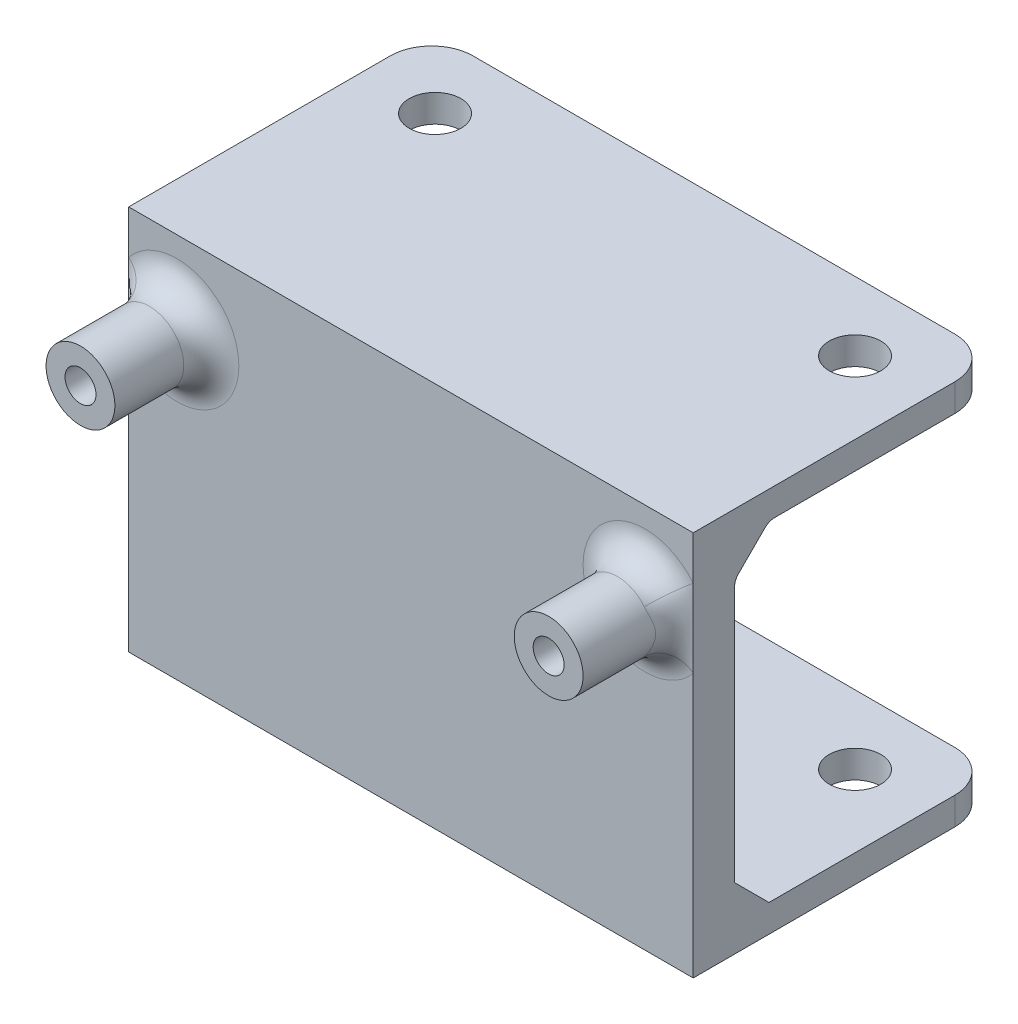
SolidWorks part; units mm, degrees
ref_plane "前视基准面" through (0, 0, 0) normal (0, 0, 1) x (1, 0, 0)
ref_plane "上视基准面" through (0, 0, 0) normal (0, 1, 0) x (1, 0, 0)
ref_plane "右视基准面" through (0, 0, 0) normal (1, 0, 0) x (0, 0, -1)
other "Configuration Table"
sketch "草图1" plane through (0, 0, 0) normal (0, 1, 0) x (1, 0, 0)
  line L0 (-15.25, 6) -> (15.25, 6) construction
  line L1 (-20.5, 11) -> (20.5, 11)
  line L2 (-20.5, 11) -> (-20.5, -11)
  line L3 (-20.5, -11) -> (20.5, -11)
  line L4 (20.5, 11) -> (20.5, -11)
  line L5 (-20.5, 0) -> (20.5, 0) construction
  circle A0 centre (-15.25, 6) radius 1.875
  circle A1 centre (15.25, 6) radius 1.875
  point P10 (0, 0)
  point P11 (0, 6)
  dimension "D3" = 3.75
  dimension "D4" = 3.75
  dimension "D1" = 41
  dimension "D2" = 22
  dimension "D5" = 30.5
  dimension "D6" = 5
extrude "凸台-拉伸1" add sketch "草图1" against normal blind 2
sketch "草图2" plane through (0, 0, 11) normal (0, 0, 1) x (1, 0, 0)
  line L0 (-17, -6) -> (17, -6) construction
  line L1 (-20.5, -2) -> (20.5, -2)
  line L2 (-20.5, -2) -> (-20.5, -28)
  line L3 (-20.5, -28) -> (20.5, -28)
  line L4 (20.5, -2) -> (20.5, -28)
  circle A0 centre (-17, -6) radius 1.125
  circle A1 centre (17, -6) radius 1.125
  point P4 (0, -6)
  dimension "D1" = 2.25
  dimension "D2" = 2.25
  dimension "D3" = 34
  dimension "D4" = 4
  dimension "D5" = 26
extrude "凸台-拉伸2" add sketch "草图2" against normal blind 3
ref_plane "基准面2" through (20.5, -2, 8) normal (-1, 0, 0) x (0, 0, 1)
sketch "草图5" plane through (20.5, -2, 8) normal (-1, 0, 0) x (0, 0, 1)
  line L0 (-2.5, 0) -> (0, -2.5)
  line L1 (-19, 0) -> (0, 0) construction
  line L2 (0, 0) -> (0, -26) construction
  line L3 (-2.5, 0) -> (0, 0)
  line L4 (0, 0) -> (0, -2.5)
  dimension "D1" = 2.5
  dimension "D2" = 2.5
extrude "凸台-拉伸3" add sketch "草图5" along normal up to surface (41 mm away) up to face at (-20.5, -10, 2.6667)
fillet "圆角1" radius 3 2 edges at (20.5, -1, -11) (-20.5, -1, -11)
fillet "圆角2" radius 1 2 edges at (0, -4.5, 8) (0, -2, 5.5)
sketch "草图6" plane through (0, 0, 11) normal (0, 0, 1) x (1, 0, 0)
  circle A0 centre (-17, -6) radius 2.5
  circle A1 centre (17, -6) radius 2.5
  circle A2 centre (-17, -6) radius 1.125 construction
  circle A3 centre (-17, -6) radius 1.125
  circle A4 centre (17, -6) radius 1.125 construction
  circle A5 centre (17, -6) radius 1.125
  point P4 (-17, -6)
  point P5 (17, -6)
  dimension "D1" = 5
  dimension "D2" = 5
extrude "凸台-拉伸4" add sketch "草图6" along normal blind 7
fillet "圆角3" radius 2 2 edges at (19.5, -6, 11) (-14.5, -6, 11)
sketch "草图8" plane through (0, -28, 0) normal (0, -1, 0) x (1, 0, 0)
  line L4 (20.5, -8) -> (20.5, 11)
  line L5 (-17.5, -11) -> (17.5, -11)
  line L6 (-20.5, 11) -> (-20.5, -8)
  line L7 (20.5, 11) -> (-20.5, 11)
  line L8 (20.5, -8) -> (20.5, 11)
  line L9 (-17.5, -11) -> (17.5, -11)
  line L10 (-20.5, 11) -> (-20.5, -8)
  line L11 (20.5, 11) -> (-20.5, 11)
  circle A0 centre (-15.25, -6) radius 1.875 construction
  circle A1 centre (15.25, -6) radius 1.875 construction
  arc A2 (17.5, -11) -> (20.5, -8) centre (17.5, -8) ccw
  arc A3 (-20.5, -8) -> (-17.5, -11) centre (-17.5, -8) ccw
  arc A4 (17.5, -11) -> (20.5, -8) centre (17.5, -8) ccw
  arc A5 (-20.5, -8) -> (-17.5, -11) centre (-17.5, -8) ccw
  circle A6 centre (-15.25, -6) radius 1.875
  circle A7 centre (15.25, -6) radius 1.875
  dimension "D1" = 0
extrude "凸台-拉伸5" add sketch "草图8" against normal blind 2
sketch "草图9" plane through (20.5, -2, 8) normal (-1, 0, 0) x (0, 0, 1)
  line L0 (0, -21.5) -> (-2.5, -24)
  line L1 (0, -2.9142) -> (0, -24) construction
  line L2 (0, -24) -> (-16, -24) construction
  line L3 (-2.5, -24) -> (0, -24)
  line L4 (0, -24) -> (0, -21.5)
  dimension "D1" = 2.5
extrude "凸台-拉伸6" add sketch "草图9" along normal up to surface (41 mm away) up to face at (-20.5, -10.4088, 3.5912)
